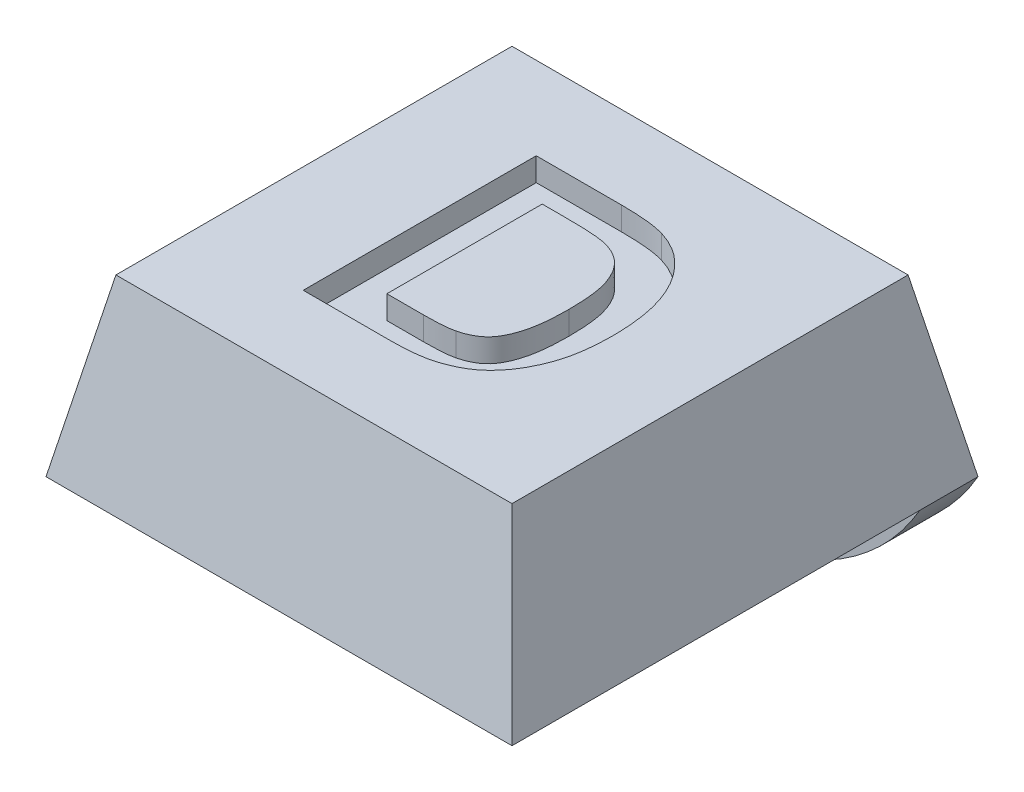
SolidWorks part; units mm, degrees
ref_plane "Front Plane" through (0, 0, 0) normal (0, 0, 1) x (1, 0, 0)
ref_plane "Top Plane" through (0, 0, 0) normal (0, 1, 0) x (1, 0, 0)
ref_plane "Right Plane" through (0, 0, 0) normal (1, 0, 0) x (0, 0, -1)
sketch "Sketch1" plane through (0, 0, 0) normal (0, 1, 0) x (1, 0, 0)
  line L1 (0, 0) -> (8, 0)
  line L2 (0, 0) -> (0, 8)
  line L3 (0, 8) -> (8, 8)
  line L4 (8, 0) -> (8, 8)
  dimension "D1" = 8
  dimension "D2" = 8
extrude "Boss-Extrude1" add sketch "Sketch1" along normal blind 3
sketch "Sketch2" plane through (0, 0, 0) normal (0, 0, 1) x (1, 0, 0)
  line L0 (0, 0) -> (0.6, 3)
  line L1 (0, 3) -> (8, 3) construction
  line L2 (0.6, 3) -> (0, 3)
  line L3 (0, 3) -> (0, 0)
  line L4 (8, 0) -> (7.4, 3)
  line L5 (7.4, 3) -> (8, 3)
  line L6 (8, 3) -> (8, 0)
  dimension "D1" = 0.6
  dimension "D2" = 0.6
extrude "Cut-Extrude1" cut sketch "Sketch2" against normal through all both and the other way through all
sketch "Sketch3" plane through (0, 0, 0) normal (1, 0, 0) x (0, 0, -1)
  line L0 (0, 0) -> (0.6, 3)
  line L1 (8, 3) -> (0, 3) construction
  line L2 (0.6, 3) -> (0, 3)
  line L3 (0, 3) -> (0, 0)
  line L4 (8, 3) -> (7.4, 3)
  line L5 (7.4, 3) -> (8, 0)
  line L6 (8, 3) -> (8, 0)
  dimension "D1" = 0.6
  dimension "D2" = 0.6
extrude "Cut-Extrude2" cut sketch "Sketch3" along normal blind 11
sketch "Sketch4" plane through (0, 0, 0) normal (0, -1, 0) x (1, 0, 0)
  line L0 (8, 0) -> (8, -8) construction
  line L3 (0, 0) -> (8, 0) construction
  circle A0 centre (4, -3.75) radius 1.8
  dimension "D1" = 3.6
  dimension "D2" = 4
  dimension "D3" = 3.75
extrude "Cut-Extrude3" cut sketch "Sketch4" against normal blind 0.8
sketch "Sketch5" plane through (0, 0, 0) normal (0, -1, 0) x (1, 0, 0)
  line L0 (8, 0) -> (8, -8) construction
  line L1 (0, -8) -> (8, -8)
  line L2 (0, -8) -> (0, -7)
  line L3 (0, -7) -> (8, -7)
  line L4 (8, -8) -> (8, -7)
  dimension "D1" = 1
extrude "Boss-Extrude2" add sketch "Sketch5" along normal blind 2
fillet "Fillet1" radius 4 2 edges at (8, -2, -7.5) (0, -2, -7.5)
sketch "Sketch6" plane through (0, 3, 0) normal (0, 1, 0) x (1, 0, 0)
  text T0 "D" font "Arial" height 4
extrude "Cut-Extrude4" cut sketch "Sketch6" against normal blind 0.4
